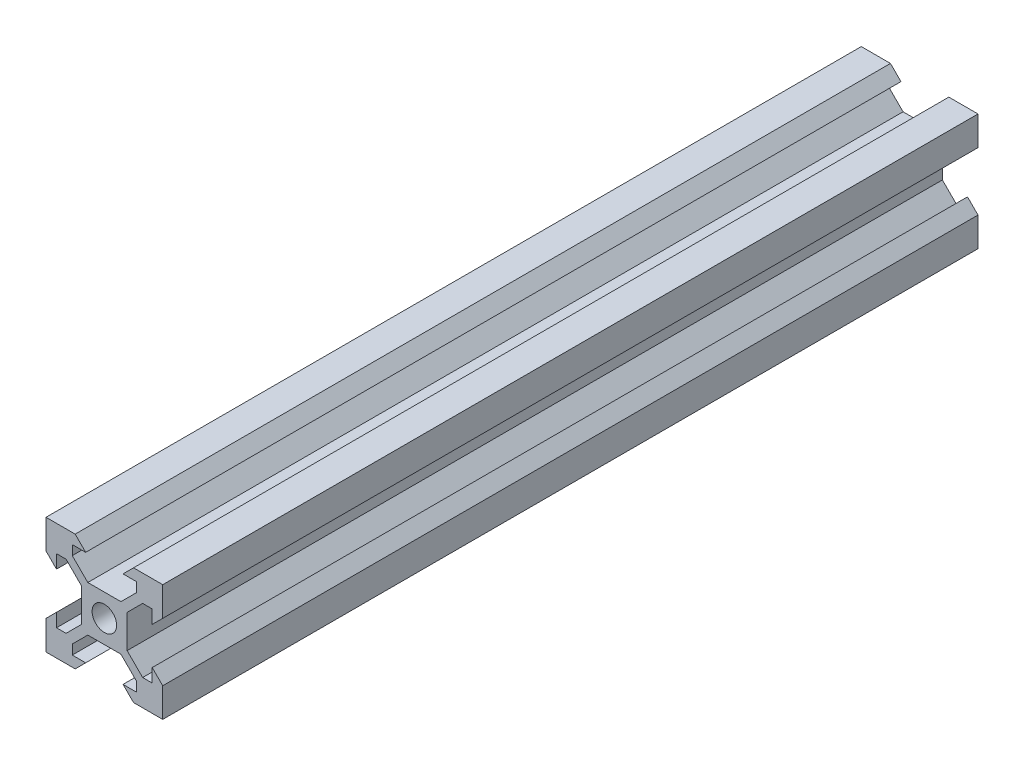
SolidWorks part; units mm, degrees
material "6063-T5"
ref_plane "Front Plane" through (0, 0, 0) normal (0, 0, 1) x (1, 0, 0)
ref_plane "Top Plane" through (0, 0, 0) normal (0, 1, 0) x (1, 0, 0)
ref_plane "Right Plane" through (0, 0, 0) normal (1, 0, 0) x (0, 0, -1)
sketch "Sketch1" plane through (0, 0, 0) normal (0, 0, 1) x (1, 0, 0)
  line L0 (-10, 10) -> (-5, 10)
  line L1 (10, -10) -> (-10, -10) construction
  line L2 (10, -10) -> (10, 10) construction
  line L3 (10, 10) -> (-10, 10) construction
  line L4 (-10, -10) -> (-10, 10) construction
  line L5 (10, -10) -> (-10, 10) construction
  line L6 (10, 10) -> (-10, -10) construction
  line L7 (-5, 10) -> (-3.2, 8.2)
  line L8 (-3.2, 8.2) -> (-5.4993, 8.2)
  line L9 (-5.4993, 8.2) -> (-5.4993, 6.56)
  line L10 (-2.84, 3.9007) -> (2.84, 3.9007)
  line L11 (0, 3.9007) -> (0, 2.1) construction
  line L12 (-5.4993, 6.56) -> (-2.84, 3.9007)
  line L13 (0, 0) -> (0, -13.2939) construction
  line L14 (0, 0) -> (-17.0802, 0) construction
  line L15 (-10, 10) -> (-10, 5)
  line L16 (-10, 5) -> (-8.2, 3.2)
  line L17 (-8.2, 3.2) -> (-8.2, 5.4993)
  line L18 (-8.2, 5.4993) -> (-6.56, 5.4993)
  line L19 (-6.56, 5.4993) -> (-3.9007, 2.84)
  line L20 (-3.9007, 2.84) -> (-3.9007, -2.84)
  line L21 (-3.2, -8.2) -> (-5.4993, -8.2)
  line L22 (-5.4993, -8.2) -> (-5.4993, -6.56)
  line L23 (-5, -10) -> (-3.2, -8.2)
  line L24 (-10, -10) -> (-5, -10)
  line L25 (-10, -10) -> (-10, -5)
  line L26 (-10, -5) -> (-8.2, -3.2)
  line L27 (-8.2, -3.2) -> (-8.2, -5.4993)
  line L28 (-8.2, -5.4993) -> (-6.56, -5.4993)
  line L29 (-6.56, -5.4993) -> (-3.9007, -2.84)
  line L30 (-5.4993, -6.56) -> (-2.84, -3.9007)
  line L31 (-2.84, -3.9007) -> (2.84, -3.9007)
  line L32 (5.4993, 6.56) -> (2.84, 3.9007)
  line L33 (3.2, 8.2) -> (5.4993, 8.2)
  line L34 (5.4993, 8.2) -> (5.4993, 6.56)
  line L35 (5, 10) -> (3.2, 8.2)
  line L36 (10, 10) -> (5, 10)
  line L37 (10, 10) -> (10, 5)
  line L38 (10, 5) -> (8.2, 3.2)
  line L39 (8.2, 3.2) -> (8.2, 5.4993)
  line L40 (8.2, 5.4993) -> (6.56, 5.4993)
  line L41 (6.56, 5.4993) -> (3.9007, 2.84)
  line L42 (3.9007, 2.84) -> (3.9007, -2.84)
  line L43 (6.56, -5.4993) -> (3.9007, -2.84)
  line L44 (8.2, -5.4993) -> (6.56, -5.4993)
  line L45 (8.2, -3.2) -> (8.2, -5.4993)
  line L46 (10, -5) -> (8.2, -3.2)
  line L47 (10, -10) -> (10, -5)
  line L48 (10, -10) -> (5, -10)
  line L49 (5, -10) -> (3.2, -8.2)
  line L50 (3.2, -8.2) -> (5.4993, -8.2)
  line L51 (5.4993, -8.2) -> (5.4993, -6.56)
  line L52 (5.4993, -6.56) -> (2.84, -3.9007)
  circle A0 centre (0, 0) radius 2.1
  arc A1 (0, -2.1) -> (0, 2.1) centre (0, 0) cw construction
  point P0 (0, 0)
  point P25 (-3.9007, 0)
  point P35 (0, 0)
  point P56 (0, -3.9007)
  dimension "D2" = 4.2
  dimension "D1" = 20
  dimension "D3" = 1.64
  dimension "D4" = 1.8
  dimension "D5" = 45
  dimension "D6" = 1.5
  dimension "D7" = 5.68
  dimension "D8" = 5
extrude "Boss-Extrude1" add sketch "Sketch1" along normal mid plane 139.7
